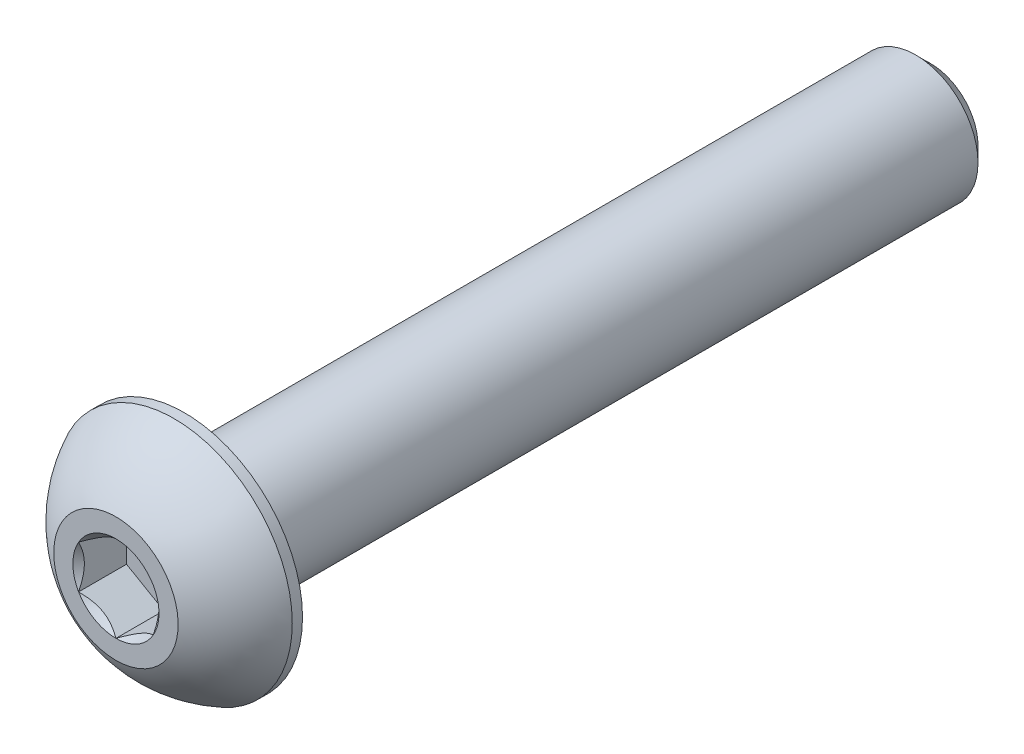
SolidWorks part; units mm, degrees
ref_plane "Front" through (0, 0, 0) normal (0, 0, 1) x (1, 0, 0)
ref_plane "Top" through (0, 0, 0) normal (0, 1, 0) x (1, 0, 0)
ref_plane "Right" through (0, 0, 0) normal (1, 0, 0) x (0, 0, -1)
sketch "Sketch1" plane through (0, 0, 0) normal (1, 0, 0) x (0, 0, -1)
  line L2 (2.75, 2.5) -> (32.75, 2.5)
  line L3 (32.75, 2.5) -> (32.75, 0)
  line L4 (32.75, 0) -> (2.75, 0)
  line L6 (2.3375, 4.75) -> (2.75, 4.75) construction
  line L7 (32.75, 2.5) -> (32.75, -2.5) construction
  line L8 (0, 0) -> (2.75, 0) construction
  line L9 (2.75, 4.75) -> (2.75, -4.75) construction
  line L11 (2.75, 2.5) -> (2.75, 0)
  line L13 (0, 1.5) -> (0, -1.5) construction
  line L14 (0, 1.5) -> (0, 2.5) construction
  line L15 (32.7, 2.5866) -> (33.1, 1.8938) construction
  line L16 (33.1, 1.8938) -> (33.5, 2.5866) construction
  line L17 (33.5, 2.5866) -> (32.7, 2.5866) construction
  line L18 (32.75, 2.5) -> (33.45, 2.5) construction
  line L19 (33.1, 2.5866) -> (33.1, 2.5) construction
  line L20 (33.1, 2.5) -> (33.1, 1.9804) construction
  line L21 (33.1, 1.9804) -> (33.1, 1.8938) construction
  line L22 (33.05, 1.9804) -> (33.15, 1.9804)
  line L23 (32.725, 2.5433) -> (33.475, 2.5433)
  line L24 (33.15, 1.9804) -> (33.475, 2.5433)
  line L25 (33.05, 1.9804) -> (32.725, 2.5433)
  line L26 (32.15, 2.5) -> (32.75, 1.9)
  arc A3 (0, 2.5) -> (2.3375, 4.75) centre (4.6581, 0) cw construction
  point P29 (33.1, 2.5433)
  point P30 (30.75, -2.5)
  dimension "D1" = 0.4125
  dimension "Pitch" = 0.8
  dimension "D3" = 0.1
  dimension "D2" = 0.6
  dimension "D4" = 45
  dimension "D5" = 2
sketch "Sketch10" plane through (0, 0, 0) normal (1, 0, 0) x (0, 0, -1)
  line L0 (32.15, 2.5) -> (32.75, 1.9) construction
  line L1 (32.15, 2.5) -> (32.75, 1.9)
  line L4 (32.75, 2.5) -> (2.75, 2.5)
  line L5 (32.75, 0) -> (32.75, 2.5)
  line L6 (2.75, 0) -> (32.75, 0)
  line L7 (2.75, 2.5) -> (2.75, 0)
  line L8 (32.15, 2.5) -> (2.75, 2.5)
  line L9 (32.75, 0) -> (32.75, 1.9)
  line L10 (2.75, 0) -> (32.75, 0)
  line L11 (2.75, 2.5) -> (2.75, 0)
  dimension "D1" = 0
revolve "Revolve3" add sketch "Sketch10" angle 360 about L8
sketch "Sketch7" plane through (0, 0, 0) normal (1, 0, 0) x (0, 0, -1)
  line L6 (2.3375, 4.75) -> (2.75, 4.75) construction
  line L8 (0, 0) -> (2.75, 0) construction
  line L11 (2.75, 4.75) -> (2.75, -4.75) construction
  line L12 (2.3375, 4.75) -> (2.75, 4.75)
  line L13 (0, 0) -> (2.75, 0)
  line L14 (0, 1.5) -> (0, -1.5) construction
  line L15 (2.75, 4.75) -> (2.75, 0)
  line L16 (0, 2.5) -> (0, 0)
  arc A2 (2.3375, 4.75) -> (0, 2.5) centre (4.6581, 0) ccw construction
  arc A3 (2.3375, 4.75) -> (0, 2.5) centre (4.6581, 0) ccw
revolve "Revolve2" add sketch "Sketch7" angle 360 mid plane about L13
sketch "Sketch5" plane through (0, 0, 0) normal (0, 0, 1) x (1, 0, 0)
  line L1 (1.5, -0.866) -> (1.5, 0.866)
  line L2 (1.5, 0.866) -> (0, 1.7321)
  line L3 (0, 1.7321) -> (-1.5, 0.866)
  line L4 (-1.5, 0.866) -> (-1.5, -0.866)
  line L5 (-1.5, -0.866) -> (0, -1.7321)
  line L6 (0, -1.7321) -> (1.5, -0.866)
  circle A0 centre (0, 0) radius 1.5 construction
extrude "Cut-Extrude2" cut sketch "Sketch5" against normal blind 1.925
sketch "Sketch6" plane through (0, 0, 0) normal (0, 0, 1) x (1, 0, 0)
  circle A0 centre (0, 0) radius 1.7321
extrude "Cut-Extrude3" cut sketch "Sketch6" against normal blind 1.925 draft 45
sketch "Sketch9" [suppressed] plane through (0, 0, -2.75) normal (0, 0, -1) x (-1, 0, 0)
  circle A0 centre (0, 0) radius 2.5 construction
  circle A4 centre (0, 0) radius 2.5
split "Split1" [suppressed] bodies to split 113
sketch "Sketch11" [suppressed] plane through (0, 0, -10.75) normal (0, 0, -1) x (-1, 0, 0)
  circle A0 centre (0, 0) radius 2.5 construction
  circle A1 centre (0, 0) radius 2.5
curve "Helix/Spiral1" [suppressed]
sketch "Sketch12" [suppressed] plane through (0, 0, 0) normal (1, 0, 0) x (0, 0, -1)
  line L0 (11.05, 1.9804) -> (11.15, 1.9804) construction
  line L1 (11.15, 1.9804) -> (11.475, 2.5433) construction
  line L2 (10.725, 2.5433) -> (11.475, 2.5433) construction
  line L3 (11.05, 1.9804) -> (10.725, 2.5433) construction
  line L4 (11.05, 1.9804) -> (11.15, 1.9804)
  line L5 (11.15, 1.9804) -> (11.475, 2.5433)
  line L6 (10.725, 2.5433) -> (11.475, 2.5433)
  line L7 (11.05, 1.9804) -> (10.725, 2.5433)
sweep "Cut-Sweep2" [suppressed] cut profiles "Sketch12" path "Helix/Spiral1"
extrude "Boss-Extrude1" [suppressed] add sketch "Sketch9" along normal blind 10 draft 45
equation "\"D1@Cut-Extrude2\" = \"Head Ht@Sketch1\" * .7"
equation "\"D1@Sketch1\" = \"Head Ht@Sketch1\" * .15"
equation "\"D1@Cut-Extrude3\" = \"D1@Cut-Extrude2\""
equation "\"D3@Sketch1\" = \"Pitch@Sketch1\" / 8"
equation "\"D2@Sketch1\"=\"Pitch@Sketch1\"*0.75"
equation "\"D3@Helix/Spiral1\" = \"Lg@Sketch1\" + \"Head Ht@Sketch1\""
equation "\"D4@Helix/Spiral1\" = \"Pitch@Sketch1\""
equation "\"D5@Sketch1\"=\"Pitch@Sketch1\"*2.5"
